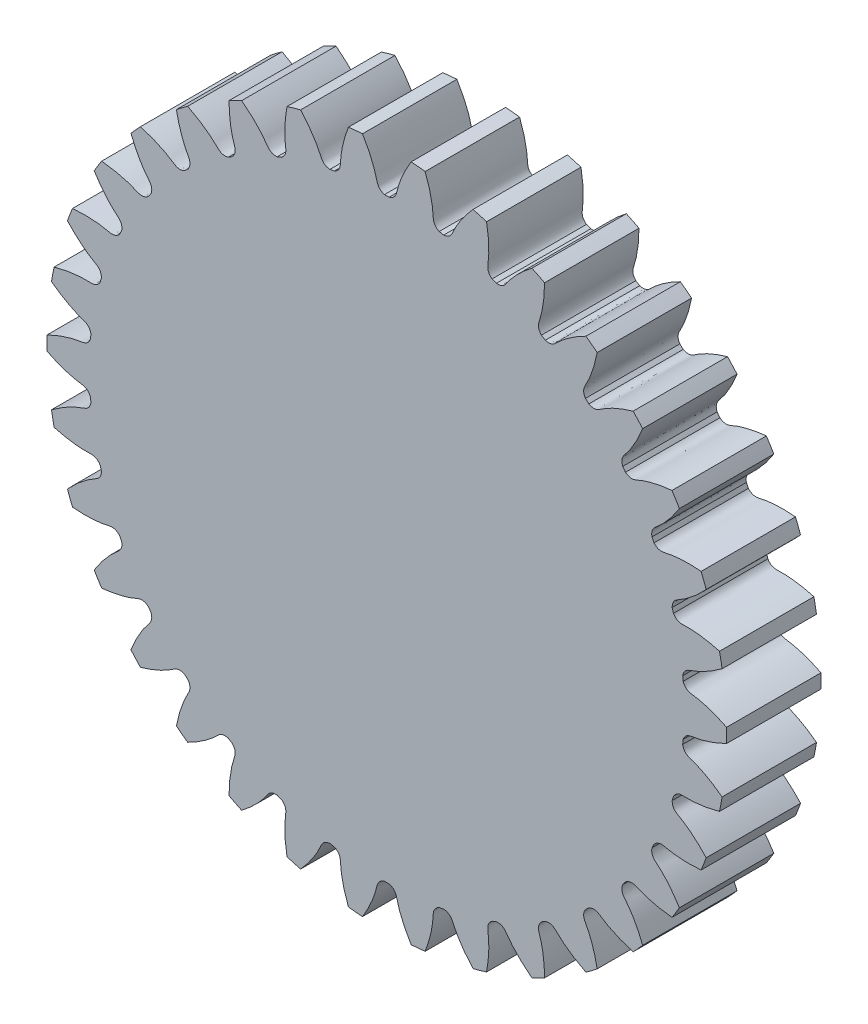
SolidWorks part; units mm, degrees
ref_plane "前视基准面" through (0, 0, 0) normal (0, 0, 1) x (1, 0, 0)
ref_plane "上视基准面" through (0, 0, 0) normal (0, 1, 0) x (1, 0, 0)
ref_plane "右视基准面" through (0, 0, 0) normal (1, 0, 0) x (0, 0, -1)
other "Configuration Table"
sketch "草图1" plane through (0, 0, 0) normal (0, 0, 1) x (1, 0, 0)
  circle A0 centre (0, 0) radius 36
extrude "凸台-拉伸1" add sketch "草图1" along normal blind 10
ref_axis "基准轴1" through (0, 0, -0.5) along (0, 0, 1)
sketch "草图2" plane through (0, 0, 0) normal (0, 0, 1) x (1, 0, 0)
  line L0 (0, 0) -> (0, 36) construction
  circle A0 centre (0, 0) radius 36 construction
  arc A1 (0.2442, 31.4991) -> (-0.2442, 31.4991) centre (0, 0) ccw
  arc A2 (6.7432, 40.7399) -> (-6.7432, 40.7399) centre (0, 0) ccw
  spline S0 degree 3 poles (0.2442, 31.4991) (0.9555, 31.7002) (1.0179, 32.2517) (1.1733, 32.8315) (1.2172, 32.9843) (1.2681, 33.1484) (1.3263, 33.3236) (1.3922, 33.5096) (1.4663, 33.7063) (1.5491, 33.9132) (1.6409, 34.1303) (1.7424, 34.3571) (1.8537, 34.5935) (1.9755, 34.839) (2.108, 35.0933) (2.2518, 35.3562) (2.4071, 35.6272) (2.5744, 35.9061) (2.754, 36.1923) (2.9463, 36.4857) (3.1516, 36.7856) (3.3704, 37.0918) (3.6028, 37.4038) (3.8493, 37.7211) (4.1101, 38.0435) (4.3855, 38.3703) (4.6759, 38.7011) (4.9814, 39.0355) (5.3024, 39.373) (5.639, 39.7131) (6.1152, 40.1753) (6.4875, 40.5153) (6.7432, 40.7399) knots 0 0 0 0 0.130724 0.143504 0.157401 0.172415 0.188546 0.205794 0.224159 0.243641 0.26424 0.285956 0.308788 0.332738 0.357805 0.383988 0.411289 0.439706 0.46924 0.499892 0.53166 0.564545 0.598547 0.633666 0.669902 0.707255 0.745725 0.785312 0.826016 0.867836 0.910774 1 1 1 1
  spline S1 degree 3 poles (-0.2442, 31.4991) (-0.9555, 31.7002) (-1.0179, 32.2517) (-1.1733, 32.8315) (-1.2172, 32.9843) (-1.2681, 33.1484) (-1.3263, 33.3236) (-1.3922, 33.5096) (-1.4663, 33.7063) (-1.5491, 33.9132) (-1.6409, 34.1303) (-1.7424, 34.3571) (-1.8537, 34.5935) (-1.9755, 34.839) (-2.108, 35.0933) (-2.2518, 35.3562) (-2.4071, 35.6272) (-2.5744, 35.9061) (-2.754, 36.1923) (-2.9463, 36.4857) (-3.1516, 36.7856) (-3.3704, 37.0918) (-3.6028, 37.4038) (-3.8493, 37.7211) (-4.1101, 38.0435) (-4.3855, 38.3703) (-4.6759, 38.7011) (-4.9814, 39.0355) (-5.3024, 39.373) (-5.639, 39.7131) (-6.1152, 40.1753) (-6.4875, 40.5153) (-6.7432, 40.7399) knots 0 0 0 0 0.130724 0.143504 0.157401 0.172415 0.188546 0.205794 0.224159 0.243641 0.26424 0.285956 0.308788 0.332738 0.357805 0.383988 0.411289 0.439706 0.46924 0.499892 0.53166 0.564545 0.598547 0.633666 0.669902 0.707255 0.745725 0.785312 0.826016 0.867836 0.910774 1 1 1 1
extrude "切除-拉伸1" cut sketch "草图2" along normal through all
pattern_circular "阵列(圆周)1" count 34 every 10.588 about axis through (0, 0, -0.5) along (0, 0, 1) of "切除-拉伸1"
sketch "草图3" plane through (0, 0, 0) normal (0, 0, 1) x (1, 0, 0)
  circle A0 centre (0, 0) radius 34 construction
  dimension "Dn" = 68
